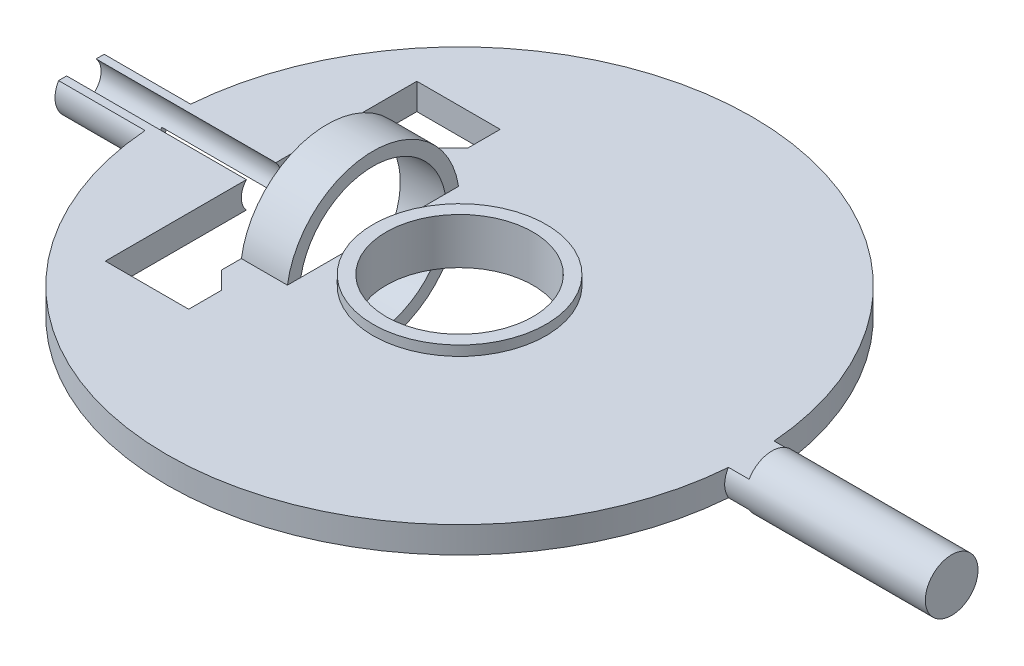
SolidWorks part; units mm, degrees
ref_plane "Front Plane" through (0, 0, 0) normal (0, 0, 1) x (1, 0, 0)
ref_plane "Top Plane" through (0, 0, 0) normal (0, 1, 0) x (1, 0, 0)
ref_plane "Right Plane" through (0, 0, 0) normal (1, 0, 0) x (0, 0, -1)
sketch "Sketch1" plane through (0, 0, 0) normal (0, 1, 0) x (1, 0, 0)
  circle A1 centre (0, 0) radius 44.45
  dimension "D1" = 88.9
extrude "Boss-Extrude1" add sketch "Sketch1" along normal mid plane 4
sketch "Sketch5" plane through (0, 0, 0) normal (0, 1, 0) x (1, 0, 0)
  circle A0 centre (0, 0) radius 11.15
  circle A1 centre (0, 0) radius 13.15
  dimension "D1" = 22.3
  dimension "D2" = 2
extrude "Boss-Extrude2" add sketch "Sketch5" along normal mid plane 7
extrude "Cut-Extrude2" cut sketch "Sketch5<2>" against normal through all both and the other way through all contours A0 region at (0, 0, 0)
sketch "Sketch5<2>" plane through (0, 0, 0) normal (0, 1, 0) x (1, 0, 0) same geometry as "Sketch5"
sketch "Sketch6" plane through (0, 0, 0) normal (0, 1, 0) x (1, 0, 0)
  line L0 (-1000, 0) -> (49000, 0) construction
  line L1 (0, 0) -> (0, 69.0003) construction
  line L2 (-47.45, 4) -> (-47.45, -4)
  line L3 (-47.45, 4) -> (-44.2697, 4)
  line L4 (-47.45, -4) -> (-44.2697, -4)
  line L5 (47.45, -4) -> (44.2697, -4)
  line L6 (47.45, 4) -> (47.45, -4)
  line L7 (47.45, 4) -> (44.2697, 4)
  circle A0 centre (0, 0) radius 47.45 construction
  circle A1 centre (0, 0) radius 44.45 construction
  circle A2 centre (0, 0) radius 44.45
  point P11 (-47.45, 0)
  dimension "D1" = 3
  dimension "D2" = 8
extrude "Boss-Extrude4" add sketch "Sketch6" along normal mid plane 4 contours A2 L3 L2 L4 | A2 L5 L6 L7 region at (-45.9195, 0, 0) region at (45.9195, 0, 0)
sketch "Sketch7" plane through (-47.45, 0, 0) normal (-1, 0, 0) x (0, 0, 1)
  circle A0 centre (0, 0) radius 4
  dimension "D1" = 8
extrude "Cut-Extrude-Thin1" cut sketch "Sketch7" against normal up to surface (3.7258 mm away) thin contours A0 up to face at (0, 0, -24.225) thin type one direction wall 4
extrude "Boss-Extrude6" add sketch "Sketch7<3>" along normal blind 30 contours A0
sketch "Sketch7<3>" plane through (-47.45, 0, 0) normal (-1, 0, 0) x (0, 0, 1) same geometry as "Sketch7"
mirror "Mirror2" about plane through (0, 0, 0) normal (1, 0, 0) of "Cut-Extrude-Thin1"
sketch "Sketch11" plane through (47.45, 0, 0) normal (1, 0, 0) x (0, 0, -1)
  circle A0 centre (0, 0) radius 4
  dimension "D1" = 8
extrude "Boss-Extrude7" add sketch "Sketch11" along normal blind 27.3
sketch "Sketch13" plane through (-77.45, 0, 0) normal (-1, 0, 0) x (0, 0, 1)
  circle A0 centre (0, 0) radius 3
  circle A1 centre (0, 0) radius 4 construction
  dimension "D1" = 6
extrude "Cut-Extrude3" cut sketch "Sketch13" against normal up to surface (64.6468 mm away) up to face at (0, 2, 13.15)
ref_plane "Plane1" through (-13.15, 0, 0) normal (-1, 0, 0) x (0, 0, 1)
sketch "Sketch15" plane through (-13.15, 0, 0) normal (-1, 0, 0) x (0, 0, 1)
  circle A0 centre (0, 0) radius 13.15
  circle A1 centre (0, 0) radius 11.15
  dimension "D1" = 22.3
  dimension "D2" = 2
extrude "Boss-Extrude8" add sketch "Sketch15" along normal blind 7
extrude "Cut-Extrude4" cut sketch "Sketch15<2>" along normal blind 17 contours A1
sketch "Sketch15<2>" plane through (-13.15, 0, 0) normal (-1, 0, 0) x (0, 0, 1) same geometry as "Sketch15"
sketch "Sketch20" plane through (0, 0, 0) normal (0, 1, 0) x (1, 0, 0)
  line L0 (-5.0299, -12.15) -> (-20.15, -12.15) construction
  line L1 (-20.15, 12.997) -> (-20.15, -12.997) construction
  line L2 (-20.15, -12.15) -> (-20.15, -16.0509)
  line L3 (-20.15, -16.0509) -> (-17.4893, -18.7116)
  line L4 (-20.15, -16.0509) -> (-21.4053, -17.3063) construction
  line L5 (-17.4893, -23.6615) -> (-30.15, -23.6615)
  line L6 (-30.15, -23.6615) -> (-30.15, 23.6615)
  line L7 (-20.15, -12.15) -> (-20.15, 0)
  line L8 (0, 0) -> (3.3862, 0) construction
  line L9 (-20.15, 16.0509) -> (-17.4893, 18.7116)
  line L10 (-17.4893, 23.6615) -> (-30.15, 23.6615)
  line L11 (-20.15, 12.15) -> (-20.15, 16.0509)
  line L12 (-5.0299, 12.15) -> (-20.15, 12.15) construction
  line L13 (-20.15, 12.15) -> (-20.15, 0)
  line L14 (-30.15, -2.2361) -> (-30.15, -10.9692) construction
  line L15 (-17.4893, -23.6615) -> (-17.4893, -18.7116)
  line L16 (-17.4893, 23.6615) -> (-17.4893, 18.7116)
  circle A0 centre (0, 0) radius 13.15 construction
  point P20 (-30.15, 0)
  dimension "D1" = 12.15
  dimension "D2" = 135
  dimension "D3" = 90
extrude "Cut-Extrude8" cut sketch "Sketch20" against normal through all both and the other way through all
sketch "Sketch23" plane through (-47.45, 0, 0) normal (1, 0, 0) x (0, 0, -1)
  line L4 (-3.4641, 2) -> (-2.2361, 2)
  line L5 (2.2361, 2) -> (3.4641, 2)
  line L6 (-3.4641, 2) -> (-2.2361, 2)
  line L7 (2.2361, 2) -> (3.4641, 2)
  arc A4 (2.2361, 2) -> (-2.2361, 2) centre (0, 0) ccw
  arc A5 (3.4641, 2) -> (-3.4641, 2) centre (0, 0) ccw
  arc A6 (2.2361, 2) -> (-2.2361, 2) centre (0, 0) ccw
  arc A7 (3.4641, 2) -> (-3.4641, 2) centre (0, 0) ccw
  dimension "D1" = 0
extrude "Cut-Extrude9" cut sketch "Sketch23" against normal through all
sketch "Sketch24" plane through (-77.45, 0, 0) normal (-1, 0, 0) x (0, 0, 1)
  line L4 (-2.2361, 2) -> (-3.4641, 2)
  line L5 (3.4641, 2) -> (2.2361, 2)
  line L6 (-2.2361, 2) -> (-3.4641, 2)
  line L7 (3.4641, 2) -> (2.2361, 2)
  arc A4 (-3.4641, 2) -> (3.4641, 2) centre (0, 0) ccw
  arc A5 (-2.2361, 2) -> (2.2361, 2) centre (0, 0) ccw
  arc A6 (-3.4641, 2) -> (3.4641, 2) centre (0, 0) ccw
  arc A7 (-2.2361, 2) -> (2.2361, 2) centre (0, 0) ccw
  dimension "D1" = 0
extrude "Cut-Extrude10" cut sketch "Sketch24" against normal blind 20
